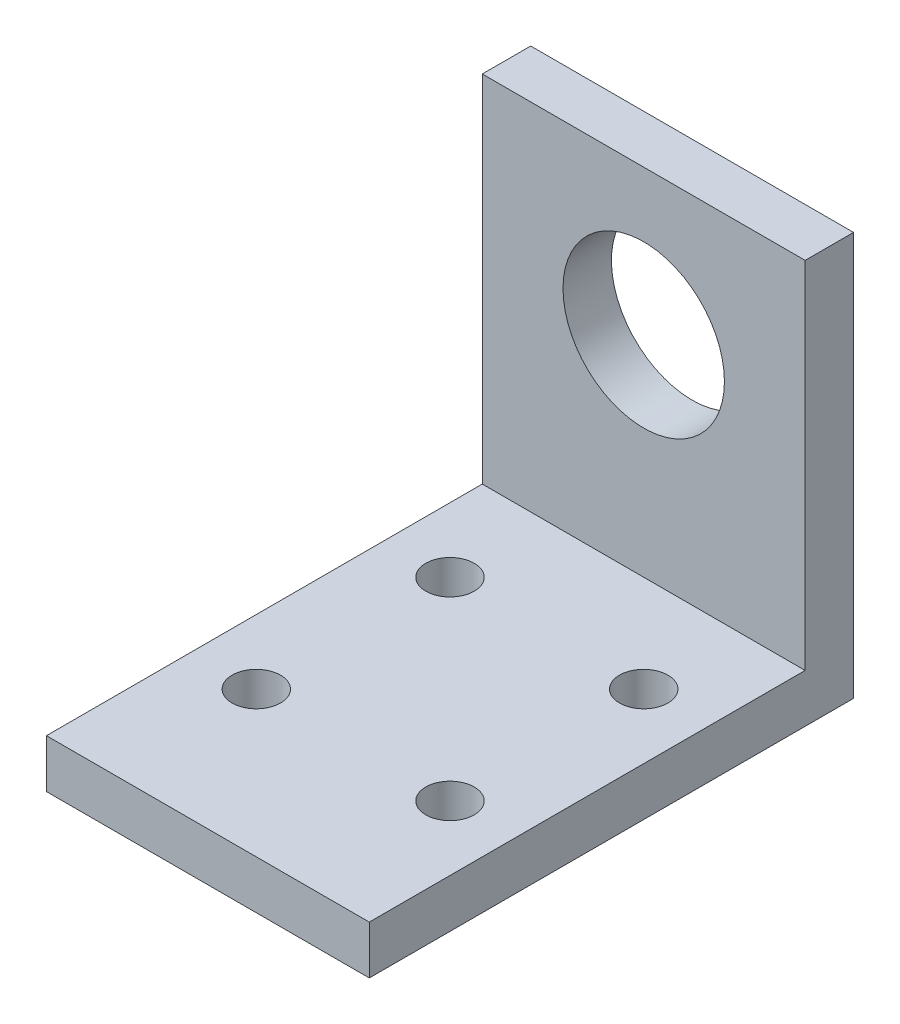
SolidWorks part; units mm, degrees
material "6063-O"
ref_plane "Front" through (0, 0, 0) normal (0, 0, 1) x (1, 0, 0)
ref_plane "Top" through (0, 0, 0) normal (0, 1, 0) x (1, 0, 0)
ref_plane "Right" through (0, 0, 0) normal (1, 0, 0) x (0, 0, -1)
sketch "草图1" plane through (0, 0, 0) normal (1, 0, 0) x (0, 0, -1)
  line L0 (0, 0) -> (0, 22)
  line L1 (0, 22) -> (3, 22)
  line L2 (3, 22) -> (3, -3)
  line L3 (3, -3) -> (-35, -3)
  line L4 (-35, -3) -> (-35, 0)
  line L5 (-35, 0) -> (0, 0)
  dimension "D1" = 22
  dimension "D2" = 3
  dimension "D3" = 25
  dimension "D4" = 38
extrude "凸台-拉伸1" add sketch "草图1" along normal blind 20
sketch "草图2" plane through (0, 0, 0) normal (0, 0, 1) x (1, 0, 0)
  line L0 (10, 22) -> (10, -3) construction
  line L1 (20, 22) -> (0, 22) construction
  line L2 (20, -3) -> (0, -3) construction
  circle A0 centre (10, 13) radius 5
  dimension "D1" = 10
  dimension "D2" = 9
extrude "切除-拉伸1" cut sketch "草图2" against normal up to next
sketch "草图3" plane through (0, 0, 0) normal (0, 1, 0) x (1, 0, 0)
  line L0 (10, 3) -> (10, -30.8482) construction
  line L1 (20, 3) -> (0, 3) construction
  circle A0 centre (4, -6) radius 1.5
  circle A1 centre (16, -6) radius 1.5
  dimension "D1" = 3
  dimension "D2" = 3
  dimension "D3" = 12
  dimension "D4" = 9
extrude "切除-拉伸2" cut sketch "草图3" against normal up to next
sketch "草图4" plane through (0, -3, 0) normal (0, -1, 0) x (1, 0, 0)
  line L0 (40, 27) -> (0, 27) construction
  line L1 (20, 27) -> (0, 27)
  line L2 (20, 27) -> (20, 35)
  line L3 (20, 35) -> (0, 35)
  line L4 (0, 27) -> (0, 35)
extrude "切除-拉伸3" cut sketch "草图4" against normal blind 10
sketch "草图5" plane through (0, -3, 0) normal (0, -1, 0) x (1, 0, 0)
  circle A0 centre (16, 18) radius 1.5
  circle A1 centre (4, 18) radius 1.5
extrude "切除-拉伸4" cut sketch "草图5" against normal blind 10
